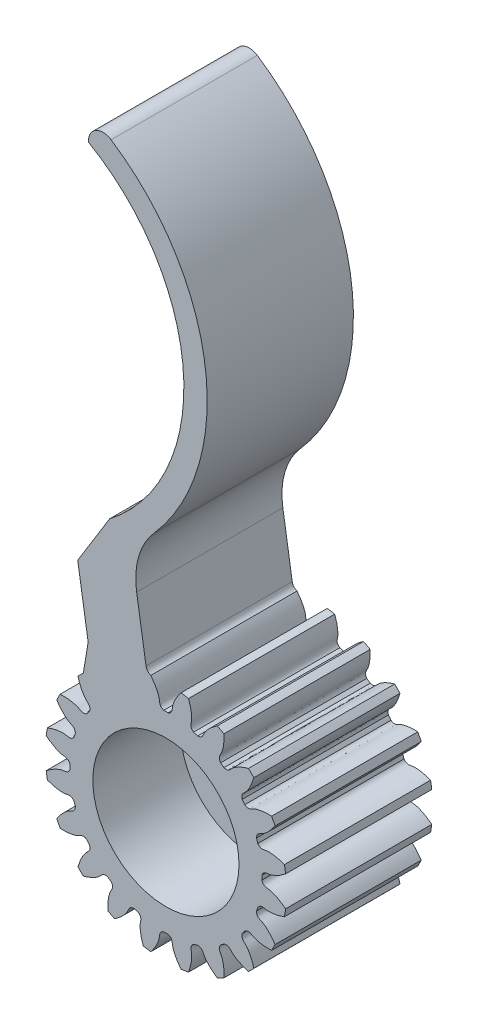
SolidWorks part; units mm, degrees
material "聚脂树脂"
ref_plane "前视基准面" through (0, 0, 0) normal (0, 0, 1) x (1, 0, 0)
ref_plane "上视基准面" through (0, 0, 0) normal (0, 1, 0) x (1, 0, 0)
ref_plane "右视基准面" through (0, 0, 0) normal (1, 0, 0) x (0, 0, -1)
other "Configuration Table"
sketch "草图1" plane through (0, 0, 0) normal (0, 0, 1) x (1, 0, 0)
  circle A0 centre (0, 0) radius 16.5
extrude "凸台-拉伸1" add sketch "草图1" along normal blind 20
ref_axis "基准轴1" through (0, 0, -1.5) along (0, 0, 1)
sketch "草图2" plane through (0, 0, 0) normal (0, 0, 1) x (1, 0, 0)
  line L0 (0, 0) -> (0, 16.5) construction
  circle A0 centre (0, 0) radius 16.5 construction
  arc A1 (0.29, 13.1218) -> (-0.29, 13.1218) centre (0, 0) ccw
  arc A2 (4.7717, 18.7474) -> (-4.7717, 18.7474) centre (0, 0) ccw
  spline S0 degree 3 poles (0.29, 13.1218) (0.9168, 13.3402) (0.8356, 13.7807) (0.9193, 14.205) (0.9283, 14.2463) (0.9395, 14.293) (0.9529, 14.3448) (0.969, 14.4018) (0.9878, 14.4638) (1.0095, 14.5309) (1.0345, 14.6028) (1.0629, 14.6795) (1.0948, 14.7608) (1.1305, 14.8467) (1.1702, 14.9371) (1.2141, 15.0317) (1.2623, 15.1305) (1.315, 15.2334) (1.3725, 15.3401) (1.4349, 15.4506) (1.5023, 15.5646) (1.575, 15.6821) (1.653, 15.8029) (1.7366, 15.9267) (1.826, 16.0534) (1.9211, 16.1829) (2.0223, 16.3149) (2.1296, 16.4493) (2.2432, 16.5859) (2.3632, 16.7244) (2.4897, 16.8646) (2.6229, 17.0065) (2.7628, 17.1496) (2.9095, 17.2939) (3.0632, 17.4391) (3.224, 17.585) (3.3918, 17.7313) (3.567, 17.8779) (3.7493, 18.0245) (3.9391, 18.1709) (4.1363, 18.3167) (4.4122, 18.5125) (4.6259, 18.6545) (4.7717, 18.7474) knots 0 0 0 0 0.165916 0.170906 0.176664 0.183189 0.190482 0.198542 0.207371 0.216967 0.22733 0.238462 0.250361 0.263027 0.276462 0.290664 0.305634 0.321371 0.337876 0.355149 0.37319 0.391998 0.411574 0.431917 0.453028 0.474907 0.497554 0.520968 0.54515 0.570099 0.595817 0.622302 0.649554 0.677575 0.706363 0.735918 0.766242 0.797333 0.829191 0.861818 0.895212 0.929373 1 1 1 1
  spline S1 degree 3 poles (-0.29, 13.1218) (-0.9168, 13.3402) (-0.8356, 13.7807) (-0.9193, 14.205) (-0.9283, 14.2463) (-0.9395, 14.293) (-0.9529, 14.3448) (-0.969, 14.4018) (-0.9878, 14.4638) (-1.0095, 14.5309) (-1.0345, 14.6028) (-1.0629, 14.6795) (-1.0948, 14.7608) (-1.1305, 14.8467) (-1.1702, 14.9371) (-1.2141, 15.0317) (-1.2623, 15.1305) (-1.315, 15.2334) (-1.3725, 15.3401) (-1.4349, 15.4506) (-1.5023, 15.5646) (-1.575, 15.6821) (-1.653, 15.8029) (-1.7366, 15.9267) (-1.826, 16.0534) (-1.9211, 16.1829) (-2.0223, 16.3149) (-2.1296, 16.4493) (-2.2432, 16.5859) (-2.3632, 16.7244) (-2.4897, 16.8646) (-2.6229, 17.0065) (-2.7628, 17.1496) (-2.9095, 17.2939) (-3.0632, 17.4391) (-3.224, 17.585) (-3.3918, 17.7313) (-3.567, 17.8779) (-3.7493, 18.0245) (-3.9391, 18.1709) (-4.1363, 18.3167) (-4.4122, 18.5125) (-4.6259, 18.6545) (-4.7717, 18.7474) knots 0 0 0 0 0.165916 0.170906 0.176664 0.183189 0.190482 0.198542 0.207371 0.216967 0.22733 0.238462 0.250361 0.263027 0.276462 0.290664 0.305634 0.321371 0.337876 0.355149 0.37319 0.391998 0.411574 0.431917 0.453028 0.474907 0.497554 0.520968 0.54515 0.570099 0.595817 0.622302 0.649554 0.677575 0.706363 0.735918 0.766242 0.797333 0.829191 0.861818 0.895212 0.929373 1 1 1 1
extrude "切除-拉伸1" cut sketch "草图2" along normal through all
pattern_circular "阵列(圆周)1" count 20 over 360 about axis through (0, 0, -1.5) along (0, 0, 1) of "切除-拉伸1"
sketch "草图3" plane through (0, 0, 0) normal (0, 0, 1) x (1, 0, 0)
  circle A0 centre (0, 0) radius 15 construction
  dimension "Dn" = 30
sketch "草图4" plane through (0, 0, 20) normal (0, 0, 1) x (1, 0, 0)
  line L0 (0, 0) -> (0, 24.252) construction
  line L1 (0, 0) -> (-4.1504, 26.2048) construction
  line L2 (-14.6667, -3.2847) -> (-22.6322, 47.0071) construction
  line L3 (-12.7072, 29.0903) -> (-7.9015, -1.2515)
  line L4 (-4.8057, 30.3418) -> (0, 0)
  line L5 (-11.2693, 79.2123) -> (-10.5853, 75.2708)
  line L6 (-11.294, 12.029) -> (-10.6385, 16.029)
  line L7 (-3.0932, 16.2075) -> (-2.5812, 16.2969)
  line L8 (0, 0) -> (-34.8237, -5.5155) construction
  line L9 (-7.9015, -1.2515) -> (0, 0)
  circle A0 centre (0, 0) radius 12.5 construction
  circle A1 centre (-23.5381, 52.727) radius 29.189 construction
  arc A2 (-2.0665, 16.3701) -> (-3.0932, 16.2075) centre (0, 0) ccw construction
  arc A3 (-4.8057, 30.3418) -> (-11.2693, 79.2123) centre (-23.5381, 52.727) ccw
  circle A4 centre (-23.5381, 52.727) radius 26 construction
  arc A6 (-12.7072, 29.0903) -> (-10.5853, 75.2708) centre (-23.5381, 52.727) ccw
  arc A8 (-3.7791, 12.5692) -> (-4.3306, 12.39) centre (0, 0) ccw construction
  arc A9 (-7.024, 14.9303) -> (-7.9502, 14.4584) centre (0, 0) ccw construction
  arc A10 (-7.4782, 10.7862) -> (-7.9474, 10.4453) centre (0, 0) ccw construction
  arc A12 (-3.7791, 12.5692) -> (-4.3306, 12.39) centre (0, 0) ccw
  arc A13 (-7.024, 14.9303) -> (-7.9502, 14.4584) centre (0, 0) ccw
  arc A14 (-7.4782, 10.7862) -> (-7.9474, 10.4453) centre (0, 0) ccw
  spline S0 degree 3 poles (2295.3671, 1929.7263) (-117.6975, -134.774) (-40.8912, 20.8175) (-11.0168, 11.9483) (-10.7713, 11.8675) (-10.4966, 11.7648) (-10.2471, 11.6599) (-10.0224, 11.5547) (-9.822, 11.4509) (-9.671, 11.3649) (-9.5386, 11.2841) (-9.4441, 11.2225) (-9.3578, 11.1623) (-9.3008, 11.1209) (-9.2491, 11.0817) (-9.2026, 11.0451) (-9.1503, 11.0021) (-9.105, 10.9626) (-4.5559, 6.7443) (-24.7562, -23.4769) (1867.2073, 2351.7135) knots -12.160638 -12.160638 -12.160638 -12.160638 0.502446 0.525093 0.568083 0.608002 0.644851 0.678629 0.709336 0.736973 0.749639 0.77267 0.783033 0.792629 0.801458 0.809518 0.816811 0.829094 0.834084 3.350793 3.350793 3.350793 3.350793 only from (-11.294, 12.029) to (-7.9474, 10.4453) construction
  spline S1 degree 3 poles (-3000.2151, -128.3054) (33.5455, 6.2288) (-2.7783, 7.6499) (-3.5171, 13.8097) (-3.5224, 13.8696) (-3.5265, 13.9372) (-3.5289, 13.9963) (-3.5307, 14.0865) (-3.5293, 14.2134) (-3.5206, 14.3824) (-3.5033, 14.5733) (-3.4754, 14.7858) (-3.4352, 15.0192) (-3.381, 15.2729) (-3.3111, 15.5461) (-3.2398, 15.7847) (-3.1737, 15.9845) (7.1936, 45.3178) (178.2143, 16.0013) (-2910.3372, -722.7198) knots -2.350827 -2.350827 -2.350827 -2.350827 0.165916 0.170906 0.183189 0.190482 0.198542 0.207371 0.22733 0.250361 0.276462 0.305634 0.337876 0.37319 0.411574 0.453028 0.474907 0.497554 13.160601 13.160601 13.160601 13.160601 only from (-3.7791, 12.5692) to (-3.0932, 16.2075) construction
  spline S2 degree 3 poles (2779.3421, 1125.9713) (-153.5845, -91.8071) (-32.4569, 32.4347) (-6.7853, 14.7679) (-6.5768, 14.6152) (-6.3474, 14.4326) (-6.1425, 14.2557) (-5.9612, 14.0862) (-5.8028, 13.9257) (-5.6857, 13.7971) (-5.5848, 13.6794) (-5.514, 13.5916) (-5.4504, 13.5077) (-5.409, 13.4507) (-5.3719, 13.3975) (-5.3391, 13.3482) (-5.3027, 13.2912) (-5.2717, 13.2396) (-2.2488, 7.822) (-30.7993, -14.6778) (2502.5391, 1659.6136) knots -12.160638 -12.160638 -12.160638 -12.160638 0.502446 0.525093 0.568083 0.608002 0.644851 0.678629 0.709336 0.736973 0.749639 0.77267 0.783033 0.792629 0.801458 0.809518 0.816811 0.829094 0.834084 3.350793 3.350793 3.350793 3.350793 only from (-7.024, 14.9303) to (-4.3306, 12.39) construction
  spline S3 degree 3 poles (-2813.7256, -1049.1431) (29.9789, 16.29) (-5.0063, 6.4169) (-7.6124, 12.047) (-7.636, 12.1023) (-7.6607, 12.1653) (-7.6812, 12.2208) (-7.7108, 12.3061) (-7.7487, 12.4272) (-7.7927, 12.5905) (-7.8352, 12.7775) (-7.8743, 12.9882) (-7.9082, 13.2226) (-7.9351, 13.4806) (-7.9531, 13.762) (-7.959, 14.011) (-7.9578, 14.2215) (-7.1625, 45.3227) (164.5472, 70.2894) (-2544.5625, -1586.6911) knots -2.350827 -2.350827 -2.350827 -2.350827 0.165916 0.170906 0.183189 0.190482 0.198542 0.207371 0.22733 0.250361 0.276462 0.305634 0.337876 0.37319 0.411574 0.453028 0.474907 0.497554 13.160601 13.160601 13.160601 13.160601 only from (-7.4782, 10.7862) to (-7.9502, 14.4584) construction
  spline S4 degree 3 poles (-3.7791, 12.5692) (-3.2504, 12.9706) (-3.4637, 13.3644) (-3.5171, 13.8097) (-3.5224, 13.8696) (-3.5265, 13.9372) (-3.5289, 13.9963) (-3.5307, 14.0865) (-3.5293, 14.2134) (-3.5206, 14.3824) (-3.5033, 14.5733) (-3.4754, 14.7858) (-3.4352, 15.0192) (-3.381, 15.2729) (-3.3111, 15.5461) (-3.224, 15.8378) (-3.1479, 16.0599) (-3.1017, 16.1848) (-3.0932, 16.2075) knots 0 0 0 0 0.165916 0.170906 0.183189 0.190482 0.198542 0.207371 0.22733 0.250361 0.276462 0.305634 0.337876 0.37319 0.411574 0.453028 0.497554 0.507432 0.507432 0.507432 0.507432
  spline S5 degree 3 poles (-7.024, 14.9303) (-6.9129, 14.8568) (-6.7202, 14.7228) (-6.459, 14.5233) (-6.2419, 14.3433) (-6.0489, 14.1699) (-5.8792, 14.0047) (-5.7318, 13.8492) (-5.6234, 13.7255) (-5.5309, 13.613) (-5.4664, 13.5298) (-5.409, 13.4507) (-5.3719, 13.3975) (-5.3391, 13.3482) (-5.3027, 13.2912) (-5.2717, 13.2396) (-5.0532, 12.848) (-4.9943, 12.404) (-4.3306, 12.39) knots 0.492568 0.492568 0.492568 0.492568 0.546972 0.588426 0.62681 0.662124 0.694366 0.723538 0.749639 0.761538 0.783033 0.792629 0.801458 0.809518 0.816811 0.829094 0.834084 1 1 1 1
  spline S6 degree 3 poles (-7.4782, 10.7862) (-7.0995, 11.3313) (-7.424, 11.64) (-7.6124, 12.047) (-7.636, 12.1023) (-7.6607, 12.1653) (-7.6812, 12.2208) (-7.7108, 12.3061) (-7.7487, 12.4272) (-7.7927, 12.5905) (-7.8352, 12.7775) (-7.8743, 12.9882) (-7.9082, 13.2226) (-7.9351, 13.4806) (-7.9531, 13.762) (-7.9603, 14.0664) (-7.9566, 14.3011) (-7.9513, 14.4342) (-7.9502, 14.4584) knots 0 0 0 0 0.165916 0.170906 0.183189 0.190482 0.198542 0.207371 0.22733 0.250361 0.276462 0.305634 0.337876 0.37319 0.411574 0.453028 0.497554 0.507432 0.507432 0.507432 0.507432
  spline S7 degree 3 poles (-11.294, 12.029) (-11.1656, 11.9934) (-10.9409, 11.9255) (-10.6308, 11.8165) (-10.3687, 11.7125) (-10.1316, 11.6072) (-9.9192, 11.5025) (-9.7309, 11.4002) (-9.5896, 11.316) (-9.4669, 11.2376) (-9.3798, 11.1783) (-9.3008, 11.1209) (-9.2491, 11.0817) (-9.2026, 11.0451) (-9.1503, 11.0021) (-9.105, 10.9626) (-8.7761, 10.6576) (-8.5829, 10.2536) (-7.9474, 10.4453) knots 0.492568 0.492568 0.492568 0.492568 0.546972 0.588426 0.62681 0.662124 0.694366 0.723538 0.749639 0.761538 0.783033 0.792629 0.801458 0.809518 0.816811 0.829094 0.834084 1 1 1 1
  dimension "D6" = 52
  dimension "D7" = 76
  dimension "D5" = 30.72
  dimension "D10" = 25
  dimension "D9" = 80
  dimension "D1" = 9
  dimension "D2" = 15
  dimension "D3" = 8
  dimension "D4" = 30.72
  dimension "D8" = 4
extrude "凸台-拉伸2" add sketch "草图4" against normal blind 20 contours S7 A14 S6 A13 S5 A12 S4 L7 A6 | S7 region at (3.146, 51.5009, 20) region at (-10.6183, 13.2048, 20)
fillet "圆角1" radius 1 1 edges
fillet "圆角2" radius 2 1 edges at (-11.2693, 79.2123, 10)
fillet "圆角4" radius 10 1 edges at (-4.8057, 30.3418, 10)
sketch "草图5" plane through (0, 0, 20) normal (0, 0, 1) x (1, 0, 0)
  circle A0 centre (0, 0) radius 2
  dimension "D1" = 4
extrude "切除-拉伸2" cut sketch "草图5" against normal blind 20
chamfer "倒角1" distance 5 angle 45 1 edges at (-12.7072, 29.0903, 10) first distance on face at (-11.6728, 22.5596, 10)
sketch "草图6" plane through (0, 0, 20) normal (0, 0, 1) x (1, 0, 0)
  circle A0 centre (0, 0) radius 10
  dimension "D1" = 20
extrude "切除-拉伸3" cut sketch "草图6" against normal blind 12
sketch "草图7" plane through (0, 0, 0) normal (0, 0, -1) x (-1, 0, 0)
  circle A0 centre (0, 0) radius 4.5
  circle A1 centre (0, 0) radius 2
  dimension "D1" = 9
  dimension "D2" = 4
extrude "凸台-拉伸3" add sketch "草图7" along normal blind 4.5
fillet "圆角5" radius 1 1 edges at (4.5, 0, 0)
